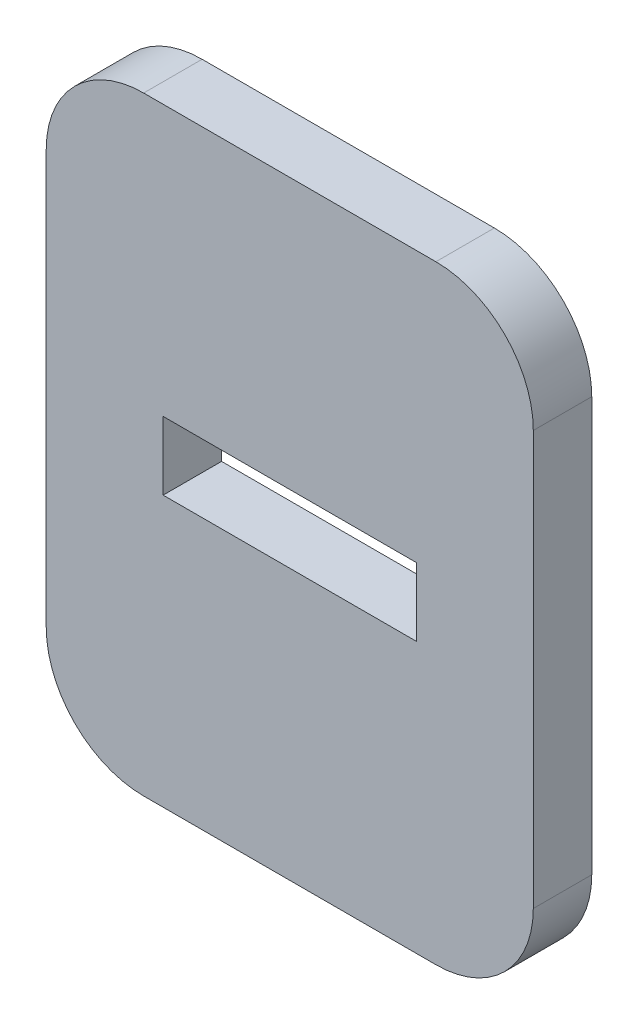
SolidWorks part; units mm, degrees
material "Plain Carbon Steel"
ref_plane "Front Plane" through (0, 0, 0) normal (0, 0, 1) x (1, 0, 0)
ref_plane "Top Plane" through (0, 0, 0) normal (0, 1, 0) x (1, 0, 0)
ref_plane "Right Plane" through (0, 0, 0) normal (1, 0, 0) x (0, 0, -1)
sketch "Sketch1" plane through (0, 0, 0) normal (0, 0, 1) x (1, 0, 0)
  line L0 (-1135.7574, 0) -> (48864.2426, 0) construction
  line L1 (-135.7574, -1000.0105) -> (-135.7574, 48999.9895) construction
  line L11 (-148.4574, -15.875) -> (-123.0574, -15.875)
  line L12 (-148.4574, -15.875) -> (-148.4574, 15.875)
  line L13 (-148.4574, 15.875) -> (-123.0574, 15.875)
  line L14 (-129.4074, 1.524) -> (-142.1074, 1.524) construction
  line L15 (-129.4074, -1.524) -> (-142.1074, -1.524) construction
  line L16 (-142.1074, -1.524) -> (-142.1074, 1.524) construction
  line L17 (-129.4074, -1.524) -> (-129.4074, 1.524) construction
  line L22 (-123.0574, -15.875) -> (-123.0574, 15.875)
  line L23 (-148.4574, -15.875) -> (-123.0574, 15.875) construction
  line L24 (-148.4574, 15.875) -> (-123.0574, -15.875) construction
  line L57 (-142.3614, 1.778) -> (-142.3614, -1.778)
  line L58 (-142.3614, -1.778) -> (-129.1534, -1.778)
  line L59 (-129.1534, -1.778) -> (-129.1534, 1.778)
  line L60 (-129.1534, 1.778) -> (-142.3614, 1.778)
  line L61 (-142.3614, 1.778) -> (-142.3614, -1.778)
  line L62 (-142.3614, -1.778) -> (-129.1534, -1.778)
  line L63 (-129.1534, -1.778) -> (-129.1534, 1.778)
  line L64 (-129.1534, 1.778) -> (-142.3614, 1.778)
  point P0 (-135.7574, 0)
  point P6 (0, 0)
  point P7 (-132.364, 0)
  dimension "D2" = 25.4
  dimension "D3" = 31.75
  dimension "D1" = 0.254
extrude "Boss-Extrude1" add sketch "Sketch1" against normal blind 3.048 contours L63 L64 L61 L62 | L13 L22 L11 L12 region at (-135.7574, 0, 0)
fillet "Fillet1" radius 5.08 4 edges at (-148.4574, -15.875, -1.524) (-123.0574, -15.875, -1.524) (-123.0574, 15.875, -1.524) (-148.4574, 15.875, -1.524)
